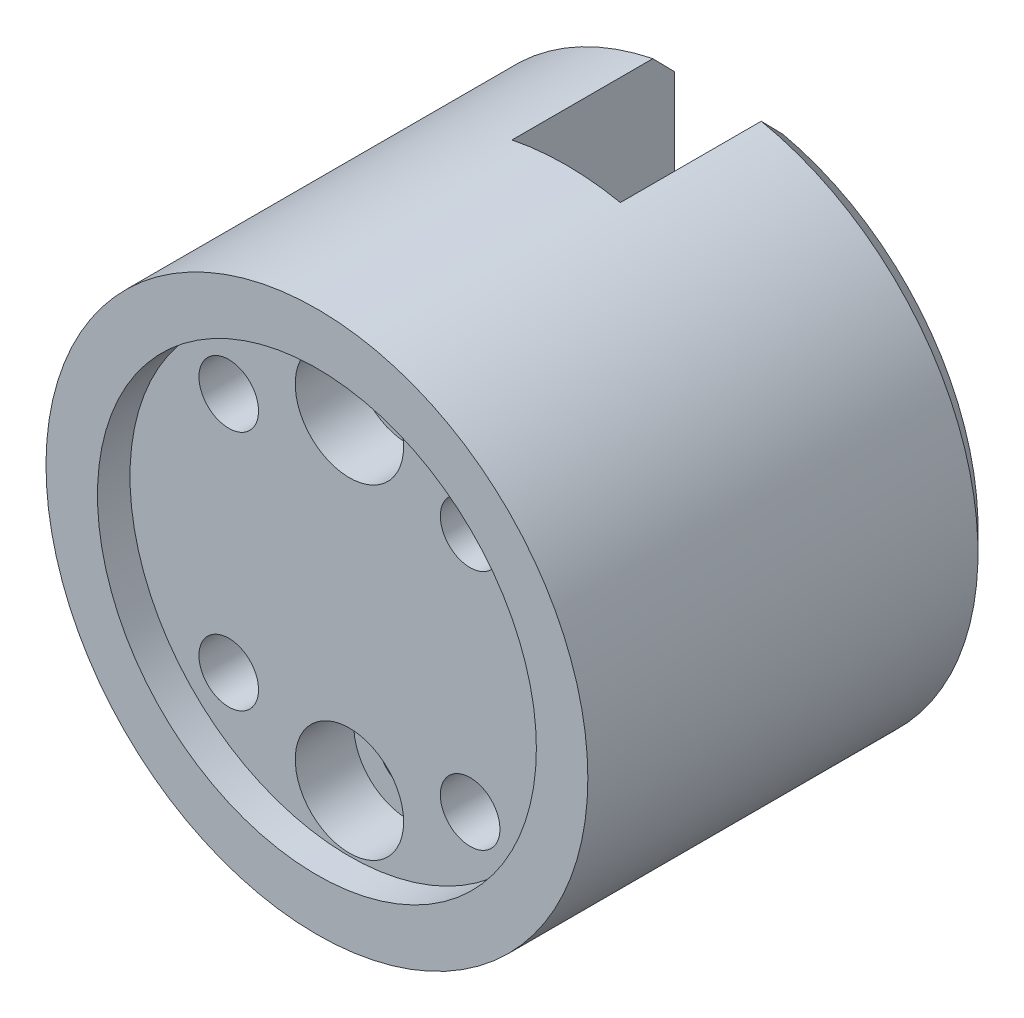
SolidWorks part; units mm, degrees
ref_plane "Front Plane" through (0, 0, 0) normal (0, 0, 1) x (1, 0, 0)
ref_plane "Top Plane" through (0, 0, 0) normal (0, 1, 0) x (1, 0, 0)
ref_plane "Right Plane" through (0, 0, 0) normal (1, 0, 0) x (0, 0, -1)
sketch "Sketch1" plane through (0, 0, 0) normal (0, 0, 1) x (1, 0, 0)
  circle A0 centre (0, 0) radius 25
  dimension "D1" = 50
extrude "Boss-Extrude1" add sketch "Sketch1" along normal blind 15
sketch "Sketch2" plane through (0, 0, 0) normal (0, 0, -1) x (-1, 0, 0)
  line L5 (0, 4) -> (2.3, 4)
  line L6 (2.3, 4.75) -> (13.4, 4.75)
  line L7 (13.4, 4.75) -> (13.4, 3)
  line L9 (2.3, 4.75) -> (2.3, 4)
  line L10 (0, 2) -> (-29.2917, 2)
  line L11 (0, 0) -> (-25.1682, 0) construction
  line L12 (0, 2) -> (0, 4)
  line L13 (13.4, 3) -> (16.4, 3)
  line L14 (16.4, 3) -> (16.4, 25)
  line L15 (16.4, 25) -> (28.3219, 25)
  line L16 (-29.2917, 2) -> (-29.2917, -2)
  line L17 (28.3219, 25) -> (28.3219, -25)
  line L18 (16.4, -25) -> (28.3219, -25)
  line L19 (16.4, -3) -> (16.4, -25)
  line L20 (13.4, -3) -> (16.4, -3)
  line L21 (0, -2) -> (0, -4)
  line L22 (0, -2) -> (-29.2917, -2)
  line L23 (2.3, -4.75) -> (2.3, -4)
  line L24 (13.4, -4.75) -> (13.4, -3)
  line L25 (2.3, -4.75) -> (13.4, -4.75)
  line L26 (0, -4) -> (2.3, -4)
  point P25 (28.3219, 0)
  point P26 (-29.2917, 0)
extrude "Cut-Extrude1" cut sketch "Sketch2" against normal blind 4
sketch "Sketch3" plane through (0, 0, 0) normal (-1, 0, 0) x (0, 0, 1)
  circle A0 centre (4, 0) radius 2
  dimension "D1" = 4
extrude "Cut-Extrude2" cut sketch "Sketch3" against normal through all
sketch "Sketch4" plane through (0, 0, 4) normal (0, 0, -1) x (-1, 0, 0)
  line L17 (0, 2) -> (0, -2)
  line L18 (0, -2) -> (0, -4)
  line L19 (0, -4) -> (2.3, -4)
  line L20 (2.3, -4) -> (2.3, -4.75)
  line L21 (2.3, -4.75) -> (13.4, -4.75)
  line L22 (13.4, -4.75) -> (13.4, -3)
  line L23 (13.4, -3) -> (16.4, -3)
  line L24 (16.4, -3) -> (16.4, -18.869)
  line L27 (16.4, 18.869) -> (16.4, 3)
  line L28 (16.4, 3) -> (13.4, 3)
  line L29 (13.4, 3) -> (13.4, 4.75)
  line L30 (13.4, 4.75) -> (2.3, 4.75)
  line L31 (2.3, 4.75) -> (2.3, 4)
  line L32 (2.3, 4) -> (0, 4)
  line L33 (0, -2) -> (0, -4)
  line L34 (0, 2) -> (0, -2)
  line L35 (0, 4) -> (0, 2)
  line L36 (0, -4) -> (2.3, -4)
  line L37 (2.3, -4) -> (2.3, -4.75)
  line L38 (2.3, -4.75) -> (13.4, -4.75)
  line L39 (13.4, -4.75) -> (13.4, -3)
  line L40 (13.4, -3) -> (16.4, -3)
  line L41 (16.4, -3) -> (16.4, -18.869)
  line L44 (16.4, 18.869) -> (16.4, 3)
  line L45 (16.4, 3) -> (13.4, 3)
  line L46 (13.4, 3) -> (13.4, 4.75)
  line L47 (13.4, 4.75) -> (2.3, 4.75)
  line L48 (2.3, 4.75) -> (2.3, 4)
  line L49 (2.3, 4) -> (0, 4)
  line L50 (0, 4) -> (0, 2)
  arc A1 (16.4, -18.869) -> (16.4, 18.869) centre (0, 0) ccw
  arc A2 (16.4, -18.869) -> (16.4, 18.869) centre (0, 0) ccw
  dimension "D1" = 0
extrude "Cut-Extrude3" cut sketch "Sketch4" against normal blind 4
fillet "Fillet1" radius 0.5 3 edges at (0, -2, 2) (0, 0, 6) (0, 2, 2)
sketch "Sketch5" plane through (0, 0, 0) normal (0, 0, -1) x (-1, 0, 0)
  circle A0 centre (0, 4) radius 0.5
  circle A1 centre (13.4, 4.75) radius 0.5
  circle A2 centre (0, -4) radius 0.5
  circle A3 centre (13.4, -4.75) radius 0.5
  dimension "D1" = 1
extrude "Cut-Extrude4" cut sketch "Sketch5" against normal blind 8
hole_wizard "Ø5.5 (5.5) Diameter Hole1" positions "Sketch7" profile "Sketch6" hole size "Ø5.5" standard "DIN" end condition through all
sketch "Sketch7" plane through (0, 0, 0) normal (0, 0, -1) x (-1, 0, 0)
  point P0 (-11.1369, 11.1369)
  point P3 (11.1369, 11.1369)
  point P6 (-11.1369, -11.1369)
  point P9 (11.1369, -11.1369)
sketch "Sketch6" plane through (11.1369, 11.1369, 0) normal (1, 0, 0) x (0, 1, 0)
  line L0 (0, 0) -> (0, 15)
  line L1 (0, 15) -> (2.75, 15)
  line L2 (2.75, 15) -> (2.75, 0)
  line L5 (2.75, 0) -> (0, 0)
  line L11 (0, -6.35) -> (0, 107.95) construction
  dimension "Thru Hole Dia." = 5.5
  dimension "Thru Hole Depth" = 15
sketch "Sketch8" plane through (0, 0, 8) normal (0, 0, -1) x (-1, 0, 0)
  line L13 (13.4, -4.25) -> (13.4, -3)
  line L14 (13.4, -3) -> (16.4, -3)
  line L15 (16.4, -3) -> (16.4, -18.869)
  line L16 (16.4, 18.869) -> (16.4, 3)
  line L17 (16.4, 3) -> (13.4, 3)
  line L18 (13.4, 3) -> (13.4, 4.25)
  line L19 (12.9, 4.75) -> (2.3, 4.75)
  line L20 (2.3, 4.75) -> (2.3, 4)
  line L21 (2.3, 4) -> (0.5, 4)
  line L22 (0, 3.5) -> (0, -3.5)
  line L23 (0.5, -4) -> (2.3, -4)
  line L24 (2.3, -4) -> (2.3, -4.75)
  line L25 (2.3, -4.75) -> (12.9, -4.75)
  line L29 (16.4, 18.869) -> (16.4, -18.869)
  arc A5 (12.9, -4.75) -> (13.4, -4.25) centre (13.4, -4.75) ccw
  arc A6 (16.4, -18.869) -> (16.4, 18.869) centre (0, 0) ccw
  arc A7 (13.4, 4.25) -> (12.9, 4.75) centre (13.4, 4.75) ccw
  arc A8 (0.5, 4) -> (0, 3.5) centre (0, 4) ccw
  arc A9 (0, -3.5) -> (0.5, -4) centre (0, -4) ccw
  arc A11 (16.4, -18.869) -> (16.4, 18.869) centre (0, 0) ccw
  dimension "D1" = 0
extrude "Cut-Extrude5" cut sketch "Sketch8" against normal through all
sketch "Sketch9" plane through (0, 0, 15) normal (0, 0, 1) x (1, 0, 0)
  circle A0 centre (0, 0) radius 20.25
  circle A1 centre (0, 0) radius 25
  dimension "D1" = 40.5
extrude "Boss-Extrude2" add sketch "Sketch9" along normal blind 3
sketch "Sketch10" plane through (0, 0, 15) normal (0, 0, -1) x (-1, 0, 0)
  line L2 (16.4, 18.869) -> (16.4, 11.8787)
  line L3 (16.4, -11.8787) -> (16.4, -18.869)
  line L4 (16.4, 18.869) -> (16.4, -18.869)
  arc A2 (16.4, -18.869) -> (16.4, 18.869) centre (0, 0) ccw
  arc A3 (16.4, -11.8787) -> (16.4, 11.8787) centre (0, 0) ccw
  arc A4 (16.4, -18.869) -> (16.4, 18.869) centre (0, 0) ccw
  dimension "D1" = 0
extrude "Boss-Extrude3" add sketch "Sketch10" along normal up to surface (7 mm away) up to face at (-7.65, 0, 8)
fillet "Fillet3" radius 1 2 edges at (-2.3, 4.75, 4) (-2.3, -4.75, 4)
fillet "Fillet4" radius 1 2 edges at (-2.3, 4, 4) (-2.3, -4, 4)
sketch "Sketch11" plane through (0, 0, 0) normal (0, 0, -1) x (-1, 0, 0)
  circle A0 centre (0, 0) radius 25
  circle A1 centre (11.1369, -11.1369) radius 2.75 construction
  circle A2 centre (11.1369, 11.1369) radius 2.75 construction
  circle A3 centre (-11.1369, -11.1369) radius 2.75 construction
  circle A4 centre (-11.1369, 11.1369) radius 2.75 construction
  circle A5 centre (11.1369, -11.1369) radius 2.75
  circle A6 centre (11.1369, 11.1369) radius 2.75
  circle A7 centre (-11.1369, -11.1369) radius 2.75
  circle A8 centre (-11.1369, 11.1369) radius 2.75
extrude "Boss-Extrude4" add sketch "Sketch11" against normal up to surface (8 mm away) up to face at (-8.4763, 0, 8)
sketch "Sketch12" plane through (0, 0, 0) normal (0, 0, -1) x (-1, 0, 0)
  line L1 (-5.15, 38.536) -> (5.15, 38.536)
  line L2 (-5.15, 38.536) -> (-5.15, -38.536)
  line L3 (-5.15, -38.536) -> (5.15, -38.536)
  line L4 (5.15, 38.536) -> (5.15, -38.536)
  line L5 (-5.15, 38.536) -> (5.15, -38.536) construction
  line L6 (-5.15, -38.536) -> (5.15, 38.536) construction
  point P0 (0, 0)
  dimension "D1" = 10.3
extrude "Cut-Extrude6" [suppressed] cut sketch "Sketch12" against normal blind 10
hole_wizard "CBORE for M5 Hex Socket Head Cap Screw1" positions "Sketch13" profile "Sketch14" counterbore size "M5" standard "DIN" end condition through all
sketch "Sketch13" plane through (0, 0, 0) normal (0, 0, -1) x (-1, 0, 0)
  point P0 (-11.1369, -11.1369)
  point P3 (-11.1369, 11.1369)
  point P6 (11.1369, -11.1369)
  point P9 (11.1369, 11.1369)
sketch "Sketch14" plane through (11.1369, -11.1369, 0) normal (1, 0, 0) x (0, 1, 0)
  line L0 (0, 0) -> (0, 18)
  line L1 (0, 18) -> (2.75, 18)
  line L3 (2.75, 18) -> (2.75, 5.4)
  line L4 (5, 5.4) -> (2.75, 5.4)
  line L5 (5, 5.4) -> (5, 0.025)
  line L6 (5, 0.025) -> (5.025, 0)
  line L7 (5.025, 0) -> (0, 0)
  line L8 (-5, 0.025) -> (-5.025, 0) construction
  line L11 (0, -6.35) -> (0, 107.95) construction
  dimension "Thru Hole Dia." = 5.5
  dimension "Thru Hole Depth" = 18
  dimension "C'Bore Dia." = 10
  dimension "C'Bore Depth" = 5.4
  dimension "Near C'Sink Dia." = 10.05
  dimension "Near C'Sink Angle" = 90
sketch "Sketch15" plane through (0, 0, 0) normal (0, 0, -1) x (-1, 0, 0)
  circle A0 centre (-11.1369, -11.1369) radius 5 construction
  circle A1 centre (0, 0) radius 25
  circle A2 centre (0, 0) radius 25
  circle A3 centre (-11.1369, -11.1369) radius 5
  circle A4 centre (-11.1369, 11.1369) radius 5.025 construction
  circle A5 centre (-11.1369, 11.1369) radius 5.025
  circle A6 centre (11.1369, -11.1369) radius 5 construction
  circle A7 centre (11.1369, -11.1369) radius 5
  circle A8 centre (11.1369, 11.1369) radius 5 construction
  circle A9 centre (11.1369, 11.1369) radius 5
  dimension "D1" = 0
extrude "Boss-Extrude5" add sketch "Sketch15" along normal blind 20
sketch "Sketch16" plane through (0, 0, 0) normal (0, 1, 0) x (1, 0, 0)
  line L0 (5, 15) -> (5, 25) construction
  line L1 (-5, 5) -> (5, 5)
  line L2 (-5, 5) -> (-5, 21.387)
  line L3 (-5, 21.387) -> (5, 21.387)
  line L4 (5, 5) -> (5, 21.387)
extrude "Cut-Extrude7" cut sketch "Sketch16" against normal through all both and the other way through all
hole_wizard "CBORE for M5 Hex Socket Head Cap Screw2" positions "Sketch17" profile "Sketch18" counterbore size "M5" standard "DIN" end condition through all
sketch "Sketch17" plane through (0, 0, 15) normal (0, 0, 1) x (1, 0, 0)
  line L0 (0, 0) -> (0, -15) construction
  line L1 (0, 0) -> (13.5829, 0) construction
  point P0 (0, -15)
  point P14 (0, 15)
  dimension "D1" = 15
sketch "Sketch18" plane through (0, -15, 15) normal (1, 0, 0) x (0, -1, 0)
  line L0 (0, 0) -> (0, 35)
  line L1 (0, 35) -> (2.75, 35)
  line L3 (2.75, 35) -> (2.75, 5.4)
  line L4 (2.75, 5.4) -> (5, 5.4)
  line L5 (5, 5.4) -> (5, 0)
  line L7 (5, 0) -> (0, 0)
  line L11 (0, -6.35) -> (0, 107.95) construction
  dimension "Thru Hole Dia." = 5.5
  dimension "Thru Hole Depth" = 35
  dimension "C'Bore Dia." = 10
  dimension "C'Bore Depth" = 5.4
chamfer "Chamfer1" distance 2 angle 45 2 edges at (25, 0, -20) (-25, 0, -20)
